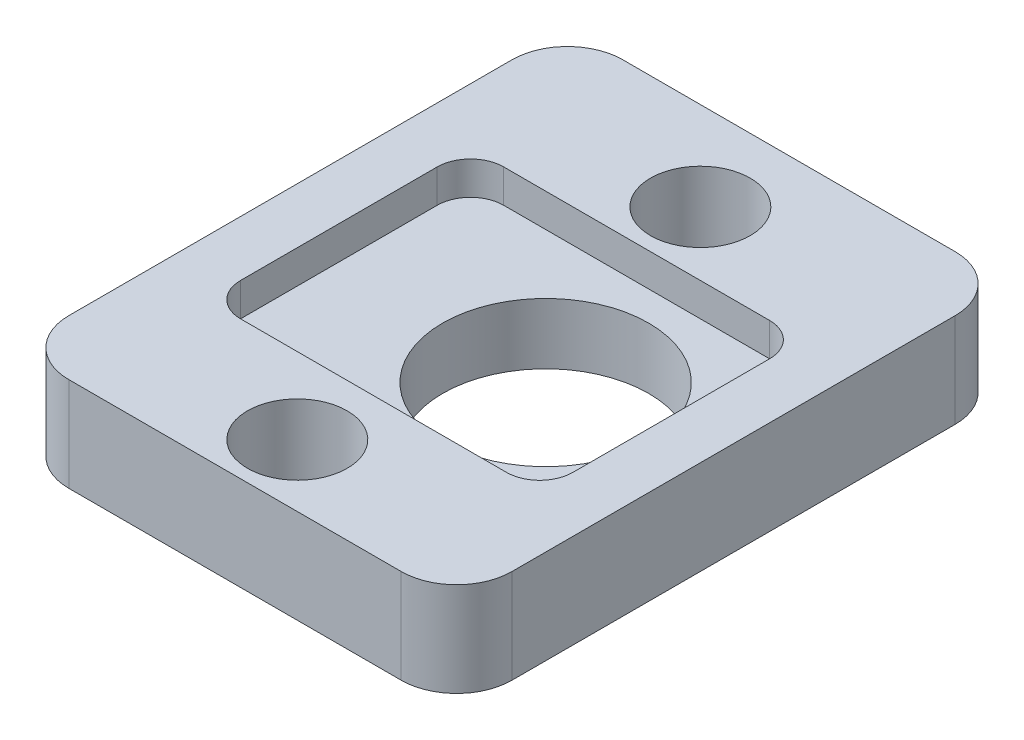
SolidWorks part; units mm, degrees
ref_plane "Front Plane" through (0, 0, 0) normal (0, 0, 1) x (1, 0, 0)
ref_plane "Top Plane" through (0, 0, 0) normal (0, 1, 0) x (1, 0, 0)
ref_plane "Right Plane" through (0, 0, 0) normal (1, 0, 0) x (0, 0, -1)
sketch "Sketch1" plane through (0, 0, 0) normal (0, 1, 0) x (1, 0, 0)
  line L1 (2, 0) -> (14, 0)
  line L2 (0, -2) -> (0, -18)
  line L3 (2, -20) -> (14, -20)
  line L4 (16, -2) -> (16, -18)
  arc A0 (0, -18) -> (2, -20) centre (2, -18) ccw
  arc A1 (14, -20) -> (16, -18) centre (14, -18) ccw
  arc A2 (14, 0) -> (16, -2) centre (14, -2) cw
  arc A3 (2, 0) -> (0, -2) centre (2, -2) ccw
  point P7 (0, -20)
  point P12 (16, 0)
  point P15 (0, 0)
  dimension "D3" = 2
  dimension "D1" = 16
  dimension "D2" = 20
extrude "Boss-Extrude1" add sketch "Sketch1" along normal blind 3.4
sketch "Sketch2" plane through (0, 3.4, 0) normal (0, 1, 0) x (1, 0, 0)
  line L0 (14, 0) -> (2, 0) construction
  line L1 (3.2, -5.5) -> (12.8, -5.5)
  line L2 (2, -6.7) -> (2, -13.8)
  line L3 (3.2, -15) -> (12.8, -15)
  line L4 (14, -6.7) -> (14, -13.8)
  line L5 (16, -18) -> (16, -2) construction
  arc A0 (2, -13.8) -> (3.2, -15) centre (3.2, -13.8) ccw
  arc A1 (12.8, -15) -> (14, -13.8) centre (12.8, -13.8) ccw
  arc A2 (12.8, -5.5) -> (14, -6.7) centre (12.8, -6.7) cw
  arc A3 (3.2, -5.5) -> (2, -6.7) centre (3.2, -6.7) ccw
  point P4 (8, -5.5)
  point P9 (2, -15)
  point P14 (14, -5.5)
  point P17 (2, -5.5)
  dimension "D4" = 1.2
  dimension "D1" = 12
  dimension "D2" = 9.5
  dimension "D3" = 5.5
  dimension "D5" = 2
extrude "Cut-Extrude1" cut sketch "Sketch2" against normal blind 1.2
sketch "Sketch3" plane through (0, 2.2, 0) normal (0, 1, 0) x (1, 0, 0)
  line L0 (14, -13.8) -> (14, -6.7) construction
  circle A0 centre (9.5, -10.2854) radius 3.72
  dimension "D1" = 7.44
  dimension "D2" = 4.5
extrude "Cut-Extrude2" cut sketch "Sketch3" against normal through all
sketch "Sketch4" plane through (0, 3.4, 0) normal (0, 1, 0) x (1, 0, 0)
  line L0 (0, -10.4749) -> (25.4035, -10.4749) construction
  line L1 (0, -2) -> (0, -18) construction
  line L2 (14, 0) -> (2, 0) construction
  circle A0 centre (8, -3.2) radius 1.8
  circle A2 centre (8, -17.7498) radius 1.8
  point P10 (6.8, -3.2)
  dimension "D1" = 3.2
  dimension "D2" = 8
extrude "Cut-Extrude3" cut sketch "Sketch4" against normal through all
